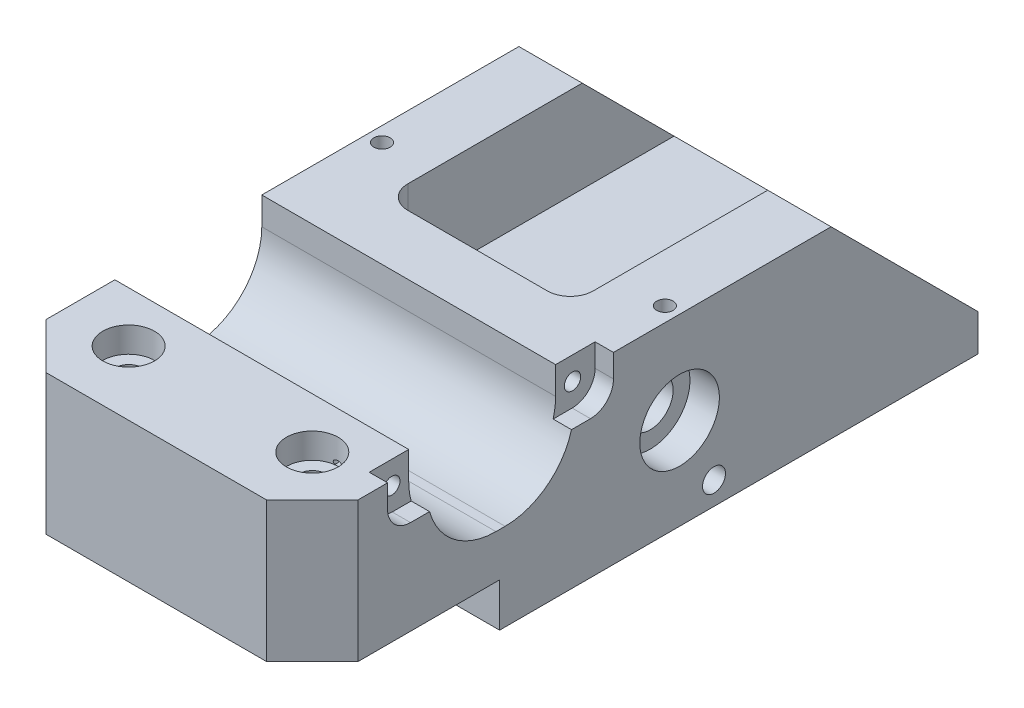
SolidWorks part; units mm, degrees
material "2024 Alloy"
ref_plane "Front Plane" through (0, 0, 0) normal (0, 0, 1) x (1, 0, 0)
ref_plane "Top Plane" through (0, 0, 0) normal (0, 1, 0) x (1, 0, 0)
ref_plane "Right Plane" through (0, 0, 0) normal (1, 0, 0) x (0, 0, -1)
sketch "Sketch1" plane through (0, 0, 0) normal (0, 1, 0) x (1, 0, 0)
  line L1 (-21.59, -46.0375) -> (21.59, -46.0375)
  line L2 (-21.59, -46.0375) -> (-21.59, 46.0375)
  line L3 (-21.59, 46.0375) -> (21.59, 46.0375)
  line L4 (21.59, -46.0375) -> (21.59, 46.0375)
  line L5 (-21.59, -46.0375) -> (21.59, 46.0375) construction
  line L6 (-21.59, 46.0375) -> (21.59, -46.0375) construction
  point P0 (0, 0)
  dimension "D1" = 43.18
  dimension "D2" = 92.075
extrude "Base" add sketch "Sketch1" along normal blind 12.7 and the other way blind 12.7
sketch "Sketch2" plane through (0, 0, -46.0375) normal (0, 0, -1) x (-1, 0, 0)
  line L1 (-21.59, -12.7) -> (21.59, -12.7) construction
  circle A0 centre (0, -12.7) radius 4.7625
  dimension "D1" = 9.525
extrude "ShaftGuide" cut sketch "Sketch2" against normal blind 41.275
ref_plane "Plane1" through (0, -12.7, 0) normal (0, -1, 0) x (-1, 0, 0)
sketch "Sketch3" plane through (0, -12.7, 0) normal (0, -1, 0) x (-1, 0, 0)
  line L0 (10.922, -20.1295) -> (16.002, -20.1295)
  line L1 (21.59, -46.0375) -> (-21.59, -46.0375) construction
  line L2 (-21.59, -46.0375) -> (-21.59, 46.0375) construction
  line L3 (0, 0) -> (0, 102.0916) construction
  line L5 (-10.922, -20.1295) -> (-10.922, -3.3655)
  line L6 (-21.59, -46.0375) -> (21.59, -46.0375)
  line L7 (-10.922, -3.3655) -> (10.922, -3.3655)
  line L8 (10.922, -20.1295) -> (10.922, -3.3655)
  line L10 (-10.922, -20.1295) -> (-21.59, -20.1295)
  line L11 (-21.59, -46.0375) -> (-21.59, -20.1295)
  line L13 (21.59, -46.0375) -> (21.59, -20.1295)
  line L14 (4.7625, 46.0375) -> (4.7625, 4.7625)
  line L15 (4.7625, 4.7625) -> (-4.7625, 4.7625)
  line L16 (-4.7625, 4.7625) -> (-4.7625, 46.0375)
  line L17 (-4.7625, 46.0375) -> (-21.59, 46.0375)
  line L18 (-21.59, 46.0375) -> (-21.59, -46.0375)
  line L19 (-21.59, -46.0375) -> (21.59, -46.0375)
  line L20 (21.59, -46.0375) -> (21.59, 46.0375)
  line L21 (21.59, 46.0375) -> (4.7625, 46.0375)
  line L23 (21.59, 46.0375) -> (21.59, -46.0375) construction
  line L25 (-4.7625, 46.0375) -> (-21.59, 46.0375) construction
  line L26 (21.59, -20.1295) -> (16.002, -20.1295)
  line L28 (21.59, -46.0375) -> (21.59, 46.0375) construction
  line L29 (21.59, 46.0375) -> (4.7625, 46.0375) construction
  dimension "D6" = 21.844
  dimension "D3" = 49.403
  dimension "D7" = 16.764
  dimension "D1" = 0
extrude "ActuatorPlaneCut" cut sketch "Sketch3" against normal blind 6.0325
sketch "Sketch5" plane through (0, 0, 0) normal (0, 1, 0) x (1, 0, 0)
  line L1 (12.827, 11.1125) -> (-12.827, 11.1125)
  line L2 (12.827, -1.5875) -> (12.827, 11.1125)
  line L3 (12.827, -1.5875) -> (-12.827, -1.5875)
  line L4 (0, 0) -> (0, 121.8983) construction
  line L5 (-10.922, -3.3655) -> (10.922, -3.3655) construction
  line L6 (-12.827, -1.5875) -> (-12.827, 11.1125)
  point P17 (12.827, -1.5875)
  point P20 (12.827, 11.1125)
  dimension "D3" = 1.778
  dimension "D1" = 12.7
  dimension "D2" = 25.654
extrude "CenterSlot" cut sketch "Sketch5" along normal through all and the other way through all
fillet "CenterSlotFillet" radius 3.175 4 edges at (-12.827, 0, -11.1125) (-12.827, 0, 1.5875) (12.827, 0, 1.5875) (12.827, 0, -11.1125)
sketch "Sketch40" plane through (0, -12.7, 0) normal (0, -1, 0) x (1, 0, 0)
  line L1 (10.922, -0.9525) -> (-10.922, -0.9525)
  line L2 (10.922, -0.9525) -> (10.922, 16.9545)
  line L3 (7.747, 20.1295) -> (-7.747, 20.1295)
  line L4 (-10.922, -0.9525) -> (-10.922, 16.9545)
  line L6 (10.922, 3.3655) -> (10.922, 20.1295) construction
  line L7 (-9.652, 1.5875) -> (9.652, 1.5875) construction
  arc A0 (-7.747, 20.1295) -> (-10.922, 16.9545) centre (-7.747, 16.9545) ccw
  arc A1 (7.747, 20.1295) -> (10.922, 16.9545) centre (7.747, 16.9545) cw
  point P8 (-10.922, 20.1295)
  dimension "D1" = 3.175
  dimension "D2" = 2.54
extrude "GearBoxPit" cut sketch "Sketch40" against normal blind 11.176
sketch "Sketch60" plane through (0, 12.7, 0) normal (0, 1, 0) x (1, 0, 0)
  line L0 (21.59, 46.0375) -> (-21.59, 46.0375) construction
  line L1 (-12.827, 7.9375) -> (12.827, 7.9375)
  line L2 (-12.827, 7.9375) -> (-12.827, 46.0375)
  line L3 (-12.827, 46.0375) -> (12.827, 46.0375)
  line L4 (12.827, 7.9375) -> (12.827, 46.0375)
  line L5 (12.827, 1.5875) -> (12.827, 7.9375) construction
extrude "FrontCutaway" cut sketch "Sketch60" against normal blind 12.7
chamfer "ChamferFront" distance 20.32 angle 45 2 edges at (-17.2085, 12.7, -46.0375) (17.2085, 12.7, -46.0375)
sketch "Sketch67" plane through (0, -12.7, 0) normal (0, -1, 0) x (-1, 0, 0)
  line L0 (-12.3825, -5.3975) -> (12.3825, -5.3975) construction
  line L1 (-12.3825, -5.0006) -> (12.3825, -5.0006)
  line L2 (-12.3825, -5.7944) -> (12.3825, -5.7944)
  line L3 (-12.3825, -16.0655) -> (12.3825, -16.0655) construction
  line L4 (-12.3825, -15.6686) -> (12.3825, -15.6686)
  line L5 (-12.3825, -16.4624) -> (12.3825, -16.4624)
  line L6 (9.652, -1.5875) -> (-9.652, -1.5875) construction
  line L7 (0, 0.0055) -> (0, 0.7987) construction
  arc A0 (-12.3825, -5.0006) -> (-12.3825, -5.7944) centre (-12.3825, -5.3975) ccw
  arc A1 (12.3825, -5.7944) -> (12.3825, -5.0006) centre (12.3825, -5.3975) ccw
  arc A2 (-12.3825, -15.6686) -> (-12.3825, -16.4624) centre (-12.3825, -16.0655) ccw
  arc A3 (12.3825, -16.4624) -> (12.3825, -15.6686) centre (12.3825, -16.0655) ccw
  point P2 (0, -5.3975)
  point P9 (0, -16.0655)
  dimension "D1" = 0.7937
  dimension "D2" = 3.81
  dimension "D3" = 24.765
  dimension "D4" = 10.668
extrude "GearBoxSlotsH" cut sketch "Sketch67" against normal blind 2.286
sketch "Sketch55" plane through (-21.59, 0, 0) normal (-1, 0, 0) x (0, 0, 1)
  line L0 (-46.0375, -12.7) -> (20.1295, -12.7) construction
  line L1 (-11.1125, -12.7) -> (-11.1125, -7.9375) construction
  circle A0 centre (-9.525, -9.525) radius 1.5875
  dimension "D1" = 3.175
  dimension "D2" = 3.175
extrude "GuideBarHole" cut sketch "Sketch55" against normal through all
sketch "Sketch56" plane through (0, 0, 0) normal (1, 0, 0) x (0, 0, -1)
  line L0 (7.9375, -12.7) -> (1.5875, -12.7) construction
  line L1 (7.9375, -12.7) -> (1.5875, -12.7) construction
  line L2 (4.7625, -12.7) -> (4.7625, 12.7) construction
  line L3 (25.7175, 12.7) -> (-46.0375, 12.7) construction
  circle A0 centre (4.7625, 0) radius 3.175
  dimension "D1" = 6.35
extrude "PitchShaftHole" cut sketch "Sketch56" against normal through all and the other way through all
sketch "Sketch57" plane through (-21.59, 0, 0) normal (-1, 0, 0) x (0, 0, 1)
  circle A0 centre (-4.7625, 0) radius 5.5
  circle A1 centre (-4.7625, 0) radius 3.175 construction
  dimension "D1" = 11
extrude "BearingBoreR" cut sketch "Sketch57" against normal blind 4.064
mirror "BearingBoreL" about plane through (0, 0, 0) normal (1, 0, 0) of "BearingBoreR"
hole_wizard "BearingBoreSetScrews" positions "Sketch59" profile "Sketch58" tap size "#4-40" standard "ANSI Inch" end condition up to next
sketch "Sketch59" plane through (4.3433, 12.7, -10.3044) normal (0, 1, 0) x (1, 0, 0)
  line L5 (-25.9333, -0.0419) -> (-25.9333, -11.0419) construction
  line L6 (-25.9333, -0.0419) -> (-25.9333, -11.0419) construction
  line L7 (-25.9333, -5.5419) -> (17.2467, -5.5419) construction
  line L8 (17.2467, -56.3419) -> (17.2467, 15.4131) construction
  line L10 (-25.9333, 15.4131) -> (-25.9333, -56.3419) construction
  point P0 (-23.9013, -5.5419)
  point P2 (15.2147, -5.5419)
  dimension "D1" = 2.032
  dimension "D2" = 2.032
sketch "Sketch58" plane through (-19.558, 12.7, -4.7625) normal (1, 0, 0) x (0, 0, 1)
  line L0 (0, 0) -> (0, 7.2)
  line L1 (0, 7.2) -> (1.1303, 7.2)
  line L2 (1.1303, 7.2) -> (1.1303, 0)
  line L5 (1.1303, 0) -> (0, 0)
  line L11 (0, -6.35) -> (0, 107.95) construction
  dimension "Thru Tap Drill Dia." = 2.2606
  dimension "Thru Tap Drill Depth" = 7.2
cosmetic thread "Hole Thread18" parameters "D2"=2.8448
cosmetic thread "Hole Thread19" parameters "D2"=2.8448
hole_wizard "ToggleAssemHoles" positions "Sketch50" profile "Sketch49" tap size "#6-32" standard "ANSI Inch"
sketch "Sketch50" plane through (0, -12.7, 0) normal (0, -1, 0) x (-1, 0, 0)
  line L1 (4.7625, 46.0375) -> (-4.7625, 46.0375) construction
  line L2 (0, 0) -> (0, 49.3678) construction
  line L3 (-9.652, 11.1125) -> (-4.7625, 11.1125) construction
  point P0 (12.7, 23.8125)
  point P2 (-12.7, 23.8125)
  point P8 (0, 46.0375)
  dimension "D1" = 12.7
  dimension "D2" = 12.7
sketch "Sketch49" plane through (-12.7, -12.7, -23.8125) normal (1, 0, 0) x (0, 0, -1)
  line L0 (0, 0) -> (0, 10.2107)
  line L1 (0, 10.2107) -> (1.3525, 9.398)
  line L2 (1.3525, 9.398) -> (1.3525, 0)
  line L5 (1.3525, 0) -> (0, 0)
  line L10 (0, 10.2107) -> (-1.3526, 9.398) construction
  line L11 (0, -6.35) -> (0, 107.95) construction
  dimension "Tap Drill Dia." = 2.7051
  dimension "Tap Drill Depth" = 9.398
  dimension "Drill Angle" = 118
cosmetic thread "Hole Thread12" parameters "D1"=9.398, "D2"=3.5052
cosmetic thread "Hole Thread13" parameters "D1"=9.398, "D2"=3.5052
chamfer "BackChamfers" distance 6.35 angle 45 2 edges at (21.59, 3.0162, 46.0375) (-21.59, 3.0162, 46.0375)
sketch "Sketch62" plane through (-21.59, 0, 0) normal (-1, 0, 0) x (0, 0, 1)
  line L0 (-46.0375, -12.7) -> (-46.0375, -7.62) construction
  line L1 (-25.7175, 12.7) -> (39.6875, 12.7) construction
  line L2 (9.8425, 9.525) -> (9.8425, 12.7)
  line L3 (30.1625, 9.525) -> (30.1625, 12.7)
  line L4 (30.1625, 12.7) -> (9.8425, 12.7)
  line L5 (9.8425, 9.525) -> (9.8425, 8.89)
  line L6 (19.3675, -0.635) -> (20.6375, -0.635)
  line L7 (30.1625, 8.89) -> (30.1625, 9.525)
  arc A0 (9.8425, 9.525) -> (30.1625, 9.525) centre (20.0025, 9.525) ccw construction
  arc A1 (19.3675, -0.635) -> (9.8425, 8.89) centre (19.3675, 8.89) cw
  arc A2 (20.6375, -0.635) -> (30.1625, 8.89) centre (20.6375, 8.89) ccw
  dimension "D1" = 20.32
  dimension "D4" = 9.525
  dimension "D2" = 66.04
  dimension "D3" = 3.175
extrude "PitchMotorSlot" cut sketch "Sketch62" against normal through all
sketch "Sketch63" plane through (21.59, 0, 0) normal (-1, 0, 0) x (0, 0, 1)
  line L1 (4.3815, 12.7) -> (35.6235, 12.7)
  line L2 (4.3815, 12.7) -> (4.3815, 9.525)
  line L3 (7.5565, 6.35) -> (32.4485, 6.35)
  line L4 (35.6235, 12.7) -> (35.6235, 9.525)
  line L5 (30.1625, 12.7) -> (9.8425, 12.7) construction
  arc A0 (32.4485, 6.35) -> (35.6235, 9.525) centre (32.4485, 9.525) ccw
  arc A1 (7.5565, 6.35) -> (4.3815, 9.525) centre (7.5565, 9.525) cw
  point P4 (20.0025, 12.7)
  dimension "D3" = 3.175
  dimension "D1" = 31.242
  dimension "D2" = 6.35
extrude "PitchMotorMountingSlots" cut sketch "Sketch63" along normal blind 2.54
hole_wizard "PitchMotorMountingHoles" positions "Sketch65" profile "Sketch64" tap size "#4-40" standard "ANSI Inch"
sketch "Sketch65" plane through (19.05, 0, 0) normal (1, 0, 0) x (0, 0, -1)
  line L0 (-35.6235, 12.7) -> (-30.1625, 12.7) construction
  line L3 (-30.1625, 12.7) -> (-9.8425, 12.7) construction
  line L5 (-20.0025, 12.7) -> (-20.0025, 7.4827) construction
  point P0 (-32.4993, 9.525)
  point P2 (-7.5057, 9.525)
  dimension "D1" = 3.175
  dimension "D2" = 24.9936
sketch "Sketch64" plane through (19.05, 9.525, 32.4993) normal (0, 1, 0) x (0, 0, -1)
  line L0 (0, 0) -> (0, 8.2738)
  line L1 (0, 8.2738) -> (1.1303, 7.5946)
  line L2 (1.1303, 7.5946) -> (1.1303, 0)
  line L5 (1.1303, 0) -> (0, 0)
  line L10 (0, 8.2738) -> (-1.1303, 7.5946) construction
  line L11 (0, -6.35) -> (0, 107.95) construction
  dimension "Tap Drill Dia." = 2.2606
  dimension "Tap Drill Depth" = 7.5946
  dimension "Drill Angle" = 118
cosmetic thread "Hole Thread20" parameters "D1"=7.5946, "D2"=2.8448
cosmetic thread "Hole Thread21" parameters "D1"=7.5946, "D2"=2.8448
hole_wizard "GearBoxMountingHoles" positions "Sketch69" profile "Sketch68" tap size "#6-32" standard "ANSI Inch"
sketch "Sketch69" plane through (0, -12.7, 0) normal (0, -1, 0) x (-1, 0, 0)
  line L0 (-12.3825, -5.7944) -> (-10.922, -5.7944) construction
  line L1 (-10.922, -15.6686) -> (-12.3825, -15.6686) construction
  line L2 (-21.59, -5.7944) -> (-10.922, -5.7944) construction
  line L3 (-10.922, -15.6686) -> (-21.59, -15.6686) construction
  line L4 (-16.256, -15.6686) -> (-16.256, -5.7944) construction
  line L6 (0, 0) -> (0, 15.1935) construction
  line L9 (-21.59, -20.1295) -> (-21.59, 46.0375) construction
  line L10 (10.922, -5.7944) -> (21.59, -5.7944) construction
  line L11 (21.59, 46.0375) -> (21.59, -20.1295) construction
  line L13 (10.922, -15.6686) -> (21.59, -15.6686) construction
  line L14 (12.3825, -15.6686) -> (10.922, -15.6686) construction
  line L15 (10.922, -15.6686) -> (10.922, -5.7944) construction
  line L17 (16.256, -15.6686) -> (16.256, -5.7944) construction
  point P0 (-16.256, -10.7315)
  point P2 (16.256, -10.7315)
sketch "Sketch68" plane through (16.256, -12.7, 10.7315) normal (1, 0, 0) x (0, 0, -1)
  line L0 (0, 0) -> (0, 10.2107)
  line L1 (0, 10.2107) -> (1.3525, 9.398)
  line L2 (1.3525, 9.398) -> (1.3525, 0)
  line L5 (1.3525, 0) -> (0, 0)
  line L10 (0, 10.2107) -> (-1.3526, 9.398) construction
  line L11 (0, -6.35) -> (0, 107.95) construction
  dimension "Tap Drill Dia." = 2.7051
  dimension "Tap Drill Depth" = 9.398
  dimension "Drill Angle" = 118
hole_wizard "CapMountingHoles" positions "Sketch74" profile "Sketch73" counterbore size "#6" standard "ANSI Inch" end condition through all
sketch "Sketch74" plane through (-0.8379, 12.7, 8.6337) normal (0, -1, 0) x (-1, 0, 0)
  line L8 (-0.8379, -1002.5128) -> (-0.8379, 48997.4872) construction
  line L9 (14.4021, -37.4038) -> (-16.0779, -37.4038) construction
  point P0 (-13.5379, -28.5138)
  point P2 (11.8621, -28.5138)
  dimension "D1" = 25.4
  dimension "D2" = 8.89
sketch "Sketch73" plane through (12.7, 12.7, 37.1475) normal (1, 0, 0) x (0, 0, 1)
  line L0 (0, 0) -> (0, 25.4)
  line L1 (0, 25.4) -> (1.8288, 25.4)
  line L3 (1.8288, 25.4) -> (1.8288, 3.5052)
  line L4 (1.8288, 3.5052) -> (3.5725, 3.5052)
  line L5 (3.5725, 3.5052) -> (3.5725, 0)
  line L7 (3.5725, 0) -> (0, 0)
  line L11 (0, -6.35) -> (0, 107.95) construction
  dimension "Thru Hole Dia." = 3.6576
  dimension "Thru Hole Depth" = 25.4
  dimension "C'Bore Dia." = 7.145
  dimension "C'Bore Depth" = 3.5052
